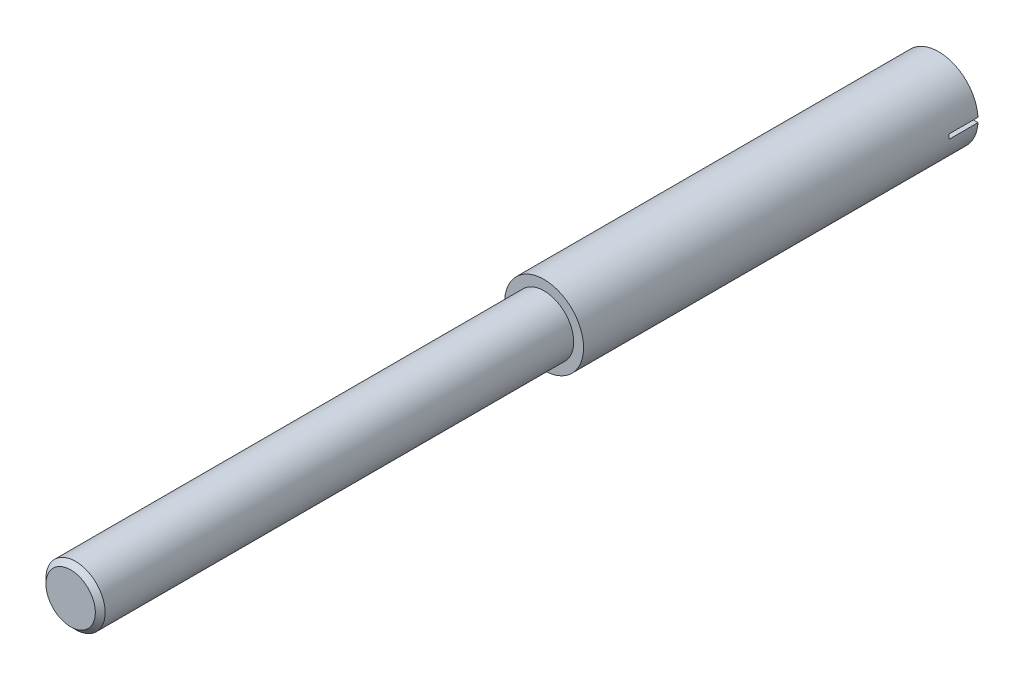
SolidWorks part; units mm, degrees
ref_plane "Front Plane" through (0, 0, 0) normal (0, 0, 1) x (1, 0, 0)
ref_plane "Top Plane" through (0, 0, 0) normal (0, 1, 0) x (1, 0, 0)
ref_plane "Right Plane" through (0, 0, 0) normal (1, 0, 0) x (0, 0, -1)
sketch "Sketch1" plane through (0, 0, 0) normal (0, 0, 1) x (1, 0, 0)
  circle A0 centre (0, 0) radius 0.5
  circle A1 centre (0, 0) radius 0.375
  dimension "D1" = 1
  dimension "D2" = 0.75
extrude "Boss-Extrude1" add sketch "Sketch1" along normal blind 5 contours A0
extrude "Boss-Extrude2" add sketch "Sketch1<3>" along normal blind 11 contours A1
sketch "Sketch1<3>" plane through (0, 0, 0) normal (0, 0, 1) x (1, 0, 0) same geometry as "Sketch1"
chamfer "Chamfer1" distance 0.062 angle 45 1 edges at (0.375, 0, 11)
sketch "Sketch2" plane through (0, 0, 0) normal (1, 0, 0) x (0, 0, -1)
  line L1 (0.37, 0.0293) -> (-0.37, 0.0293)
  line L2 (0.37, 0.0293) -> (0.37, -0.0293)
  line L3 (0.37, -0.0293) -> (-0.37, -0.0293)
  line L4 (-0.37, 0.0293) -> (-0.37, -0.0293)
  line L5 (0.37, 0.0293) -> (-0.37, -0.0293) construction
  line L6 (0.37, -0.0293) -> (-0.37, 0.0293) construction
  point P0 (0, 0)
  dimension "D1" = 0.74
  dimension "D2" = 0.0586
extrude "Cut-Extrude1" cut sketch "Sketch2" against normal through all both and the other way through all
